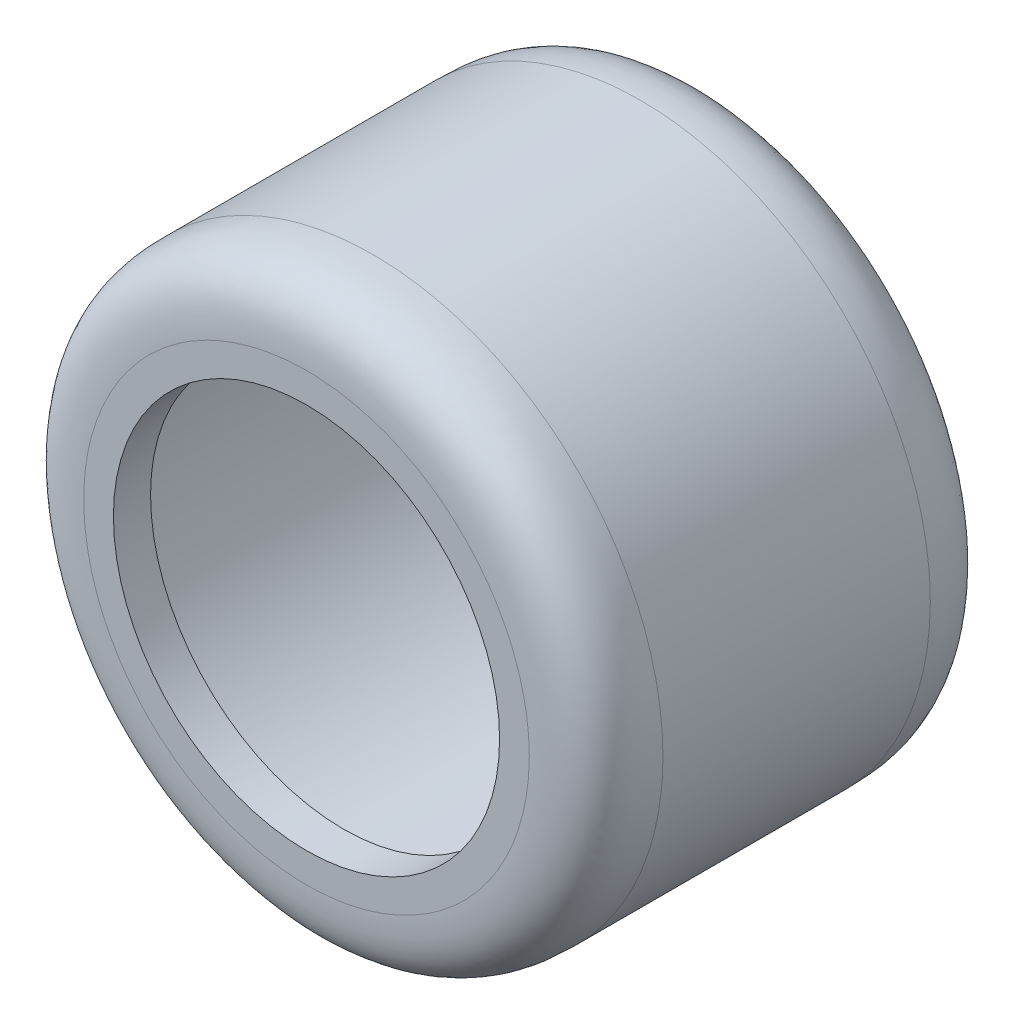
SolidWorks part; units mm, degrees
ref_plane "Plan de face" through (0, 0, 0) normal (0, 0, 1) x (1, 0, 0)
ref_plane "Plan de dessus" through (0, 0, 0) normal (0, 1, 0) x (1, 0, 0)
ref_plane "Plan de droite" through (0, 0, 0) normal (1, 0, 0) x (0, 0, -1)
sketch "Esquisse1" plane through (0, 0, 0) normal (0, 0, 1) x (1, 0, 0)
  circle A0 centre (-24.5412, 28.4516) radius 78
extrude "Boss.-Extru.1" add sketch "Esquisse1" along normal blind 108
sketch "Esquisse2" plane through (0, 0, 108) normal (0, 0, 1) x (1, 0, 0)
  circle A0 centre (-24.5412, 28.4516) radius 6.35
extrude "Enlèv. mat.-Extru.1" cut sketch "Esquisse2" against normal up to next
sketch "Esquisse3" plane through (0, 0, 108) normal (0, 0, 1) x (1, 0, 0)
  circle A0 centre (-24.5412, 28.4516) radius 52
extrude "Enlèv. mat.-Extru.2" cut sketch "Esquisse3" against normal through all
fillet "Congé1" radius 18 2 edges at (53.4588, 28.4516, 108) (53.4588, 28.4516, 0) curvature continuous yes
shell "Coque2" thickness 10 removed face at (27.4588, 28.4516, 0)
